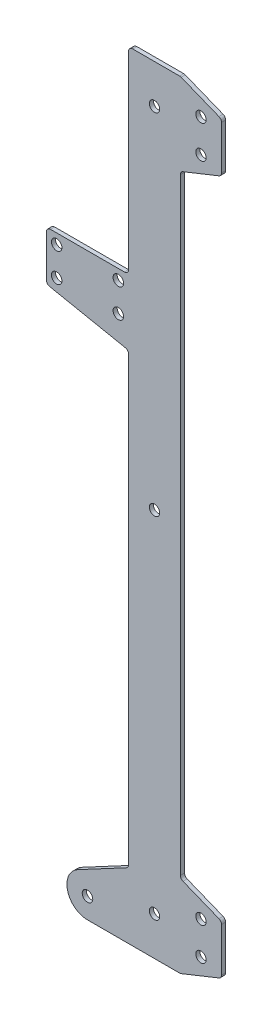
SolidWorks part; units mm, degrees
ref_plane "Front Plane" through (0, 0, 0) normal (0, 0, 1) x (1, 0, 0)
ref_plane "Top Plane" through (0, 0, 0) normal (0, 1, 0) x (1, 0, 0)
ref_plane "Right Plane" through (0, 0, 0) normal (1, 0, 0) x (0, 0, -1)
sketch "Sketch1" plane through (0, 0, 0) normal (0, 0, 1) x (1, 0, 0)
  line L1 (-10, 150) -> (10, 150)
  line L2 (-10, 150) -> (-10, -150)
  line L3 (-10, -150) -> (10, -150)
  line L4 (10, 150) -> (10, -150)
  line L5 (-10, 150) -> (10, -150) construction
  line L6 (-10, -150) -> (10, 150) construction
  point P0 (0, 0)
  dimension "D1" = 300
  dimension "20mm" = 20
extrude "Boss-Extrude1" add sketch "Sketch1" along normal blind 1.5875
sketch "Sketch2" plane through (0, 0, 1.5875) normal (0, 0, 1) x (1, 0, 0)
  line L0 (10, 150) -> (25.875, 143.65)
  line L1 (25.875, 143.65) -> (25.875, 124.6)
  line L2 (25.875, 124.6) -> (10, 118.25)
  line L3 (10, -150) -> (10, 150) construction
  line L4 (10, 118.25) -> (10, 150)
  line L5 (10, 150) -> (-10, 150) construction
  line L6 (-10, 0) -> (10, 0) construction
  line L7 (-10, 150) -> (-10, -150) construction
  line L8 (10, -118.25) -> (10, -150)
  line L9 (25.875, -124.6) -> (10, -118.25)
  line L10 (25.875, -143.65) -> (25.875, -124.6)
  line L11 (10, -150) -> (25.875, -143.65)
  circle A0 centre (17.9375, 127.775) radius 2
  circle A1 centre (17.9375, 127.775) radius 5 construction
  circle A2 centre (17.9375, 140.475) radius 2
  circle A3 centre (17.9375, -140.475) radius 2
  circle A4 centre (17.9375, -127.775) radius 5 construction
  circle A5 centre (17.9375, -127.775) radius 2
  point P3 (25.875, 134.125)
  point P8 (10, 134.125)
  point P13 (17.9375, 121.425)
  dimension "D3" = 4
  dimension "D4" = 10
  dimension "D1" = 15.875
  dimension "2.5" = 31.75
  dimension "D2" = 19.05
  dimension "D5" = 9.525
  dimension "D6" = 9.525
extrude "Boss-Extrude2" add sketch "Sketch2" against normal up to surface (1.5875 mm away) up to face at (0, 0, 0)
sketch "Sketch4" plane through (0, 0, 1.5875) normal (0, 0, 1) x (1, 0, 0)
  line L0 (0, 150) -> (0, 135) construction
  line L1 (10, 150) -> (-10, 150) construction
  line L2 (0, 135) -> (0, 0) construction
  line L3 (0, 0) -> (0, -135) construction
  line L4 (0, -135) -> (0, -150) construction
  line L5 (-10, -150) -> (10, -150) construction
  circle A0 centre (0, -135) radius 2
  circle A1 centre (0, 0) radius 2
  circle A2 centre (0, 135) radius 2
  dimension "D4" = 4
  dimension "D1" = 15
  dimension "D2" = 135
  dimension "D3" = 135
extrude "Cut-Extrude1" cut sketch "Sketch4" against normal through all
sketch "Sketch5" plane through (0, 0, 1.5875) normal (0, 0, 1) x (1, 0, 0)
  line L0 (-10, 48.4) -> (-41.75, 54.75)
  line L1 (-10, 150) -> (-10, -150) construction
  line L2 (-41.75, 54.75) -> (-41.75, 73.8)
  line L3 (-41.75, 73.8) -> (-10, 73.8)
  line L4 (-10, 73.8) -> (-10, 48.4)
  line L5 (10, 150) -> (-10, 150) construction
  line L6 (-41.75, 69.8313) -> (-37.7813, 69.8313) construction
  line L7 (-13.9688, 69.8313) -> (-10, 69.8313) construction
  line L8 (-10, -150) -> (-25.875, -150)
  line L9 (-29.6103, -135.0588) -> (-10, -124.6)
  line L10 (-10, -124.6) -> (-10, -150)
  circle A0 centre (-13.9688, 69.8313) radius 2.032
  circle A1 centre (-13.9688, 58.7188) radius 2.032
  circle A2 centre (-37.7813, 69.8313) radius 2.032
  circle A3 centre (-37.7813, 58.7188) radius 2.032
  arc A4 (-25.875, -150) -> (-29.6103, -135.0588) centre (-25.875, -142.0625) cw
  circle A5 centre (-25.875, -142.0625) radius 2.032
  point P24 (-25.875, 73.8)
  dimension "D5" = 4.064
  dimension "D9" = 4.064
  dimension "D10" = 7.9375
  dimension "D1" = 76.2
  dimension "D2" = 19.05
  dimension "D3" = 25.4
  dimension "D4" = 31.75
  dimension "D6" = 11.1125
  dimension "D7" = 23.8125
  dimension "D8" = 3.9688
  dimension "D11" = 25.4
extrude "Boss-Extrude3" add sketch "Sketch5" against normal up to surface (1.5875 mm away) up to face at (2, -135, 0)
fillet "Fillet3" radius 1.5875 12 edges at (-10, -124.6, 0.7937) (10, -150, 0.7937) (25.875, -143.65, 0.7937) (25.875, -124.6, 0.7937) (10, -118.25, 0.7937) (25.875, 124.6, 0.7937) (10, 118.25, 0.7937) (25.875, 143.65, 0.7937) (10, 150, 0.7937) (-10, 48.4, 0.7937) (-41.75, 54.75, 0.7937) (-41.75, 73.8, 0.7937)
sketch "Sketch6" [suppressed] plane through (0, 0, 1.5875) normal (0, 0, 1) x (1, 0, 0)
  line L0 (-10, -105.55) -> (-10, -150) construction
  line L1 (-10, -150) -> (-31.3933, -134.1533) construction
  line L2 (-31.3933, -121.3967) -> (-10, -105.55) construction
  line L3 (-10, -105.55) -> (-10, -150)
  line L4 (-10, -150) -> (-31.3933, -134.1533)
  line L5 (-31.3933, -121.3967) -> (-10, -105.55)
  circle A0 centre (-26.6688, -127.775) radius 2.032 construction
  arc A1 (-31.3933, -121.3967) -> (-31.3933, -134.1533) centre (-26.6688, -127.775) ccw construction
  circle A2 centre (-26.6688, -127.775) radius 2.032
  arc A3 (-31.3933, -121.3967) -> (-31.3933, -134.1533) centre (-26.6688, -127.775) ccw
extrude "Boss-Extrude4" [suppressed] add sketch "Sketch6" against normal up to vertex up to point (-10, 73.8, 0)
fillet "Fillet4" [suppressed] radius 0.7937
fillet "Fillet5" radius 1.5875 2 edges at (-10, 150, 0.7937) (-10, 73.8, 0.7937)
